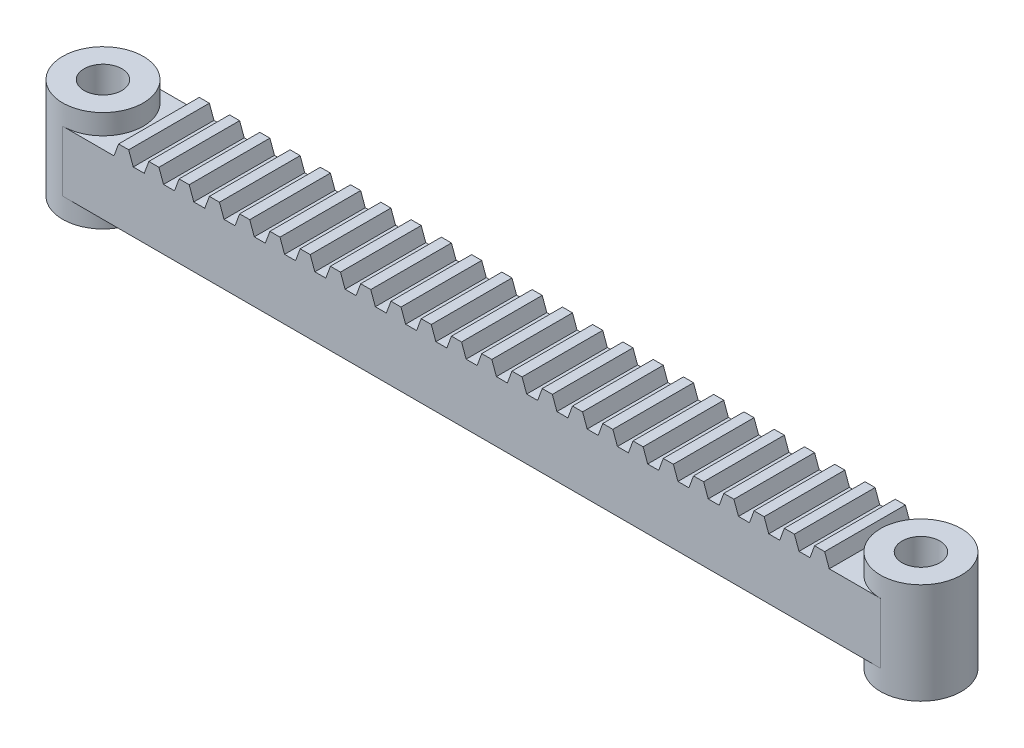
SolidWorks part; units mm, degrees
material "Galvanized Steel"
ref_plane "Front Plane" through (0, 0, 0) normal (0, 0, 1) x (1, 0, 0)
ref_plane "Top Plane" through (0, 0, 0) normal (0, 1, 0) x (1, 0, 0)
ref_plane "Right Plane" through (0, 0, 0) normal (1, 0, 0) x (0, 0, -1)
sketch "Sketch1" plane through (0, 0, 0) normal (0, 0, 1) x (1, 0, 0)
  line L0 (81.7719, 8.5) -> (83.7719, 8.5)
  line L1 (-75.138, 6) -> (-57.138, 6)
  line L3 (-75.138, -6) -> (102.6818, -6)
  line L17 (83.7719, 8.5) -> (81.7719, 8.5)
  line L19 (72.6818, 6) -> (74.862, 6)
  line L20 (81.7719, 8.5) -> (80.862, 6)
  line L21 (83.7719, 8.5) -> (84.6818, 6)
  line L22 (102.6818, 6) -> (102.6818, -6)
  line L23 (78.6818, 6) -> (80.862, 6)
  line L24 (77.7719, 8.5) -> (78.6818, 6)
  line L25 (75.7719, 8.5) -> (74.862, 6)
  line L26 (75.7719, 8.5) -> (77.7719, 8.5)
  line L27 (71.7719, 8.5) -> (72.6818, 6)
  line L28 (69.7719, 8.5) -> (68.862, 6)
  line L29 (69.7719, 8.5) -> (71.7719, 8.5)
  line L30 (65.7719, 8.5) -> (66.6818, 6)
  line L31 (63.7719, 8.5) -> (62.862, 6)
  line L32 (63.7719, 8.5) -> (65.7719, 8.5)
  line L33 (59.7719, 8.5) -> (60.6818, 6)
  line L34 (57.7719, 8.5) -> (56.862, 6)
  line L35 (57.7719, 8.5) -> (59.7719, 8.5)
  line L36 (53.7719, 8.5) -> (54.6818, 6)
  line L37 (51.7719, 8.5) -> (50.862, 6)
  line L38 (51.7719, 8.5) -> (53.7719, 8.5)
  line L39 (47.7719, 8.5) -> (48.6818, 6)
  line L40 (45.7719, 8.5) -> (44.862, 6)
  line L41 (45.7719, 8.5) -> (47.7719, 8.5)
  line L42 (41.7719, 8.5) -> (42.6818, 6)
  line L43 (39.7719, 8.5) -> (38.862, 6)
  line L44 (39.7719, 8.5) -> (41.7719, 8.5)
  line L45 (35.7719, 8.5) -> (36.6818, 6)
  line L46 (33.7719, 8.5) -> (32.862, 6)
  line L47 (33.7719, 8.5) -> (35.7719, 8.5)
  line L48 (29.7719, 8.5) -> (30.6818, 6)
  line L49 (27.7719, 8.5) -> (26.862, 6)
  line L50 (27.7719, 8.5) -> (29.7719, 8.5)
  line L51 (23.7719, 8.5) -> (24.6818, 6)
  line L52 (21.7719, 8.5) -> (20.862, 6)
  line L53 (21.7719, 8.5) -> (23.7719, 8.5)
  line L54 (17.7719, 8.5) -> (18.6818, 6)
  line L55 (15.7719, 8.5) -> (14.862, 6)
  line L56 (15.7719, 8.5) -> (17.7719, 8.5)
  line L57 (11.7719, 8.5) -> (12.6818, 6)
  line L58 (9.7719, 8.5) -> (8.862, 6)
  line L59 (9.7719, 8.5) -> (11.7719, 8.5)
  line L60 (5.7719, 8.5) -> (6.6818, 6)
  line L61 (3.7719, 8.5) -> (2.862, 6)
  line L62 (3.7719, 8.5) -> (5.7719, 8.5)
  line L63 (-0.2281, 8.5) -> (0.6818, 6)
  line L64 (-2.2281, 8.5) -> (-3.138, 6)
  line L65 (-2.2281, 8.5) -> (-0.2281, 8.5)
  line L66 (-6.2281, 8.5) -> (-5.3182, 6)
  line L67 (-8.2281, 8.5) -> (-9.138, 6)
  line L68 (-8.2281, 8.5) -> (-6.2281, 8.5)
  line L69 (-12.2281, 8.5) -> (-11.3182, 6)
  line L70 (-14.2281, 8.5) -> (-15.138, 6)
  line L71 (-14.2281, 8.5) -> (-12.2281, 8.5)
  line L72 (-18.2281, 8.5) -> (-17.3182, 6)
  line L73 (-20.2281, 8.5) -> (-21.138, 6)
  line L74 (-20.2281, 8.5) -> (-18.2281, 8.5)
  line L75 (-24.2281, 8.5) -> (-23.3182, 6)
  line L76 (-26.2281, 8.5) -> (-27.138, 6)
  line L77 (-26.2281, 8.5) -> (-24.2281, 8.5)
  line L78 (-30.2281, 8.5) -> (-29.3182, 6)
  line L79 (-32.2281, 8.5) -> (-33.138, 6)
  line L80 (-32.2281, 8.5) -> (-30.2281, 8.5)
  line L81 (-36.2281, 8.5) -> (-35.3182, 6)
  line L82 (-38.2281, 8.5) -> (-39.138, 6)
  line L83 (-38.2281, 8.5) -> (-36.2281, 8.5)
  line L84 (-42.2281, 8.5) -> (-41.3182, 6)
  line L85 (-44.2281, 8.5) -> (-45.138, 6)
  line L86 (-44.2281, 8.5) -> (-42.2281, 8.5)
  line L87 (-48.2281, 8.5) -> (-47.3182, 6)
  line L88 (-50.2281, 8.5) -> (-51.138, 6)
  line L89 (-50.2281, 8.5) -> (-48.2281, 8.5)
  line L90 (-54.2281, 8.5) -> (-53.3182, 6)
  line L91 (-56.2281, 8.5) -> (-57.138, 6)
  line L92 (-56.2281, 8.5) -> (-54.2281, 8.5)
  line L93 (-59.3182, 10.2872) -> (-59.3182, 6) construction
  line L94 (-75.138, 6) -> (-75.138, -6)
  line L95 (-53.3182, 6) -> (-51.138, 6)
  line L96 (-47.3182, 6) -> (-45.138, 6)
  line L97 (-41.3182, 6) -> (-39.138, 6)
  line L98 (-35.3182, 6) -> (-33.138, 6)
  line L99 (-29.3182, 6) -> (-27.138, 6)
  line L100 (-11.3182, 6) -> (-9.138, 6)
  line L101 (-17.3182, 6) -> (-15.138, 6)
  line L102 (-5.3182, 6) -> (-3.138, 6)
  line L103 (0.6818, 6) -> (2.862, 6)
  line L104 (-23.3182, 6) -> (-21.138, 6)
  line L105 (6.6818, 6) -> (8.862, 6)
  line L106 (12.6818, 6) -> (14.862, 6)
  line L107 (18.6818, 6) -> (20.862, 6)
  line L108 (84.6818, 6) -> (102.6818, 6)
  line L109 (66.6818, 6) -> (68.862, 6)
  line L110 (60.6818, 6) -> (62.862, 6)
  line L111 (54.6818, 6) -> (56.862, 6)
  line L112 (24.6818, 6) -> (26.862, 6)
  line L113 (30.6818, 6) -> (32.862, 6)
  line L114 (36.6818, 6) -> (38.862, 6)
  line L115 (42.6818, 6) -> (44.862, 6)
  line L116 (48.6818, 6) -> (50.862, 6)
  line L117 (86.862, 6) -> (86.862, 10.2872) construction
  point P0 (0, 0)
  dimension "D1" = 24
  dimension "D2" = 24
  dimension "D3" = 2
  dimension "D4" = 40
  dimension "D5" = 6
  dimension "D6" = 6
  dimension "D9" = 12
  dimension "D7" = 24
extrude "Boss-Extrude1" add sketch "Sketch1" along normal blind 16 contours L116 L39 L41 L40 L115 L42 L44 L43 L114 L45 L47 L46 L113 L48 L50 L49 L112 L51 L53 L52 L107 L54 L56 L55 L106 L57 L59 L58 L105 L60 L62 L61 L103 L63 L65 L64 L102 L66 L68 L67 L100 L69 L71 L70 L101 L72 L74 L73 L104 L75 L77 region at (13.7719, 0.5385, 0)
sketch "Sketch3" plane through (0, 6, 0) normal (0, 1, 0) x (1, 0, 0)
  line L1 (86.862, 0) -> (94.862, 0)
  line L2 (-59.3182, 0.9334) -> (-59.3182, -16) construction
  line L3 (-75.138, -16) -> (-57.138, -16) construction
  line L4 (86.862, 0) -> (86.862, -16)
  line L5 (84.6818, -16) -> (102.6818, -16) construction
  line L6 (-59.3182, -16) -> (-77.7063, -16)
  line L7 (-77.7063, -16) -> (-77.7063, 1.3823)
  line L8 (-77.7063, 1.3823) -> (-59.3182, 1.3823)
  line L9 (-59.3182, 1.3823) -> (-59.3182, -16)
  line L11 (86.862, -16) -> (94.862, -16)
  line L13 (94.862, 0) -> (104.4225, 2.0083)
  line L14 (104.4225, 2.0083) -> (106.3712, -17.332)
  line L15 (106.3712, -17.332) -> (91.3109, -17.9827)
  line L16 (91.3109, -17.9827) -> (94.862, -16)
  circle A0 centre (94.862, -8) radius 8
  circle A1 centre (-67.3182, -8) radius 8
  circle A2 centre (94.862, -8) radius 3.75
  circle A3 centre (-67.3182, -8) radius 3.75
  line M11 (102.6818, 0) -> (84.6818, 0)
  line M13 (84.6818, -16) -> (102.6818, -16)
  line M14 (102.6818, -16) -> (102.6818, 0)
  dimension "D1" = 16
  dimension "D2" = 16
  dimension "D3" = 7.5
  dimension "D4" = 7.5
extrude "Cut-Extrude1" cut sketch "Sketch3" against normal blind 16 contours A0 L16 L15 L14 L13 M14 M13 M11 | A0 M14 M11 | A0 M13 M14 | A2 region at (100.9066, 6, 1.6224) region at (99.6937, 6, -0.7592) region at (100.9066, 6, 14.3776)
sketch "Sketch4" plane through (0, 6, 0) normal (0, 1, 0) x (1, 0, 0)
  circle A0 centre (94.862, -8) radius 3.75 construction
  circle A1 centre (94.862, -8) radius 8 construction
  circle A2 centre (94.862, -8) radius 3.75
  circle A3 centre (94.862, -8) radius 8
extrude "Boss-Extrude2" add sketch "Sketch4" against normal blind 16
sketch "Sketch5" plane through (0, 6, 0) normal (0, 1, 0) x (1, 0, 0)
  line L3 (84.6818, -16) -> (94.862, -16)
  line L4 (94.862, 0) -> (84.6818, 0)
  line L5 (84.6818, 0) -> (84.6818, -16)
  circle A0 centre (94.862, -8) radius 3.75 construction
  arc A1 (94.862, -16) -> (94.862, 0) centre (94.862, -8) ccw
  arc A2 (94.862, -16) -> (94.862, 0) centre (94.862, -8) ccw
  circle A3 centre (94.862, -8) radius 8 construction
  circle A4 centre (94.862, -8) radius 3.75
  circle A5 centre (94.862, -8) radius 8
  arc M6 (94.862, -16) -> (94.862, 0) centre (94.862, -8) ccw
  dimension "D1" = 0
extrude "Boss-Extrude3" add sketch "Sketch5" along normal blind 4 contours A5 A4 M6 region at (87.0882, 6, 8)
sketch "Sketch6" plane through (0, 6, 0) normal (0, 1, 0) x (1, 0, 0)
  line L0 (-59.3182, 1.3823) -> (-59.3182, -16) construction
  line L1 (-59.3182, 1.3823) -> (-59.3182, -16)
  line L4 (-57.138, 0) -> (-75.138, 0)
  line L5 (-75.138, 0) -> (-75.138, -16)
  line L6 (-75.138, -16) -> (-57.138, -16)
  line L7 (-57.138, -16) -> (-57.138, 0)
  line L11 (-57.138, -16) -> (-57.138, 0)
  circle A0 centre (-67.3182, -8) radius 3.75 construction
  circle A1 centre (-67.3182, -8) radius 3.75
  circle A2 centre (-67.3182, -8) radius 8 construction
  circle A3 centre (-67.3182, -8) radius 8
  dimension "D1" = 0
extrude "Boss-Extrude4" add sketch "Sketch6" against normal blind 16 contours A1 | A3 region at (-67.3182, 6, 8)
sketch "Sketch7" plane through (0, 6, 0) normal (0, 1, 0) x (1, 0, 0)
  line L5 (-75.138, 0) -> (-75.138, -6.3118)
  line L6 (-75.138, -9.6882) -> (-75.138, -16)
  line L7 (-75.138, -16) -> (-57.138, -16)
  line L8 (-57.138, -16) -> (-57.138, 0)
  line L9 (-57.138, 0) -> (-75.138, 0)
  line L10 (-75.138, 0) -> (-75.138, -6.3118)
  line L11 (-75.138, -9.6882) -> (-75.138, -16)
  line L12 (-75.138, -16) -> (-67.3182, -16)
  line L13 (-57.138, -16) -> (-57.138, 0)
  line L14 (-67.3182, 0) -> (-75.138, 0)
  circle A0 centre (-67.3182, -8) radius 8 construction
  arc A1 (-75.138, -6.3118) -> (-75.138, -9.6882) centre (-67.3182, -8) ccw
  arc A2 (-75.138, -6.3118) -> (-75.138, -9.6882) centre (-67.3182, -8) ccw
  circle A3 centre (-67.3182, -8) radius 8
  circle A4 centre (-67.3182, -8) radius 3.75 construction
  circle A5 centre (-67.3182, -8) radius 3.75
  line M8 (-75.138, 0) -> (-75.138, -6.3118)
  line M10 (-75.138, -9.6882) -> (-75.138, -16)
  line M11 (-75.138, -16) -> (-57.138, -16)
  line M13 (-57.138, 0) -> (-75.138, 0)
  dimension "D1" = 0
extrude "Cut-Extrude2" cut sketch "Sketch7" against normal blind 16 contours A3 M13 M8 | A3 M10 M11 | A5 region at (-73.3628, 6, 1.6224) region at (-73.3628, 6, 14.3776)
sketch "Sketch8" plane through (0, 6, 0) normal (0, 1, 0) x (1, 0, 0)
  line L3 (-57.138, 0) -> (-67.3182, 0)
  line L4 (-67.3182, -16) -> (-57.138, -16)
  line L5 (-57.138, -16) -> (-57.138, 0)
  line L6 (-57.138, 0) -> (-67.3182, 0)
  line L7 (-67.3182, -16) -> (-57.138, -16)
  line L8 (-57.138, -16) -> (-57.138, 0)
  circle A0 centre (-67.3182, -8) radius 3.75 construction
  arc A1 (-67.3182, 0) -> (-67.3182, -16) centre (-67.3182, -8) ccw
  arc A2 (-67.3182, 0) -> (-67.3182, -16) centre (-67.3182, -8) ccw
  circle A3 centre (-67.3182, -8) radius 8 construction
  circle A4 centre (-67.3182, -8) radius 3.75
  circle A5 centre (-67.3182, -8) radius 8
  arc M6 (-67.3182, 0) -> (-67.3182, -16) centre (-67.3182, -8) ccw
  dimension "D1" = 0
extrude "Boss-Extrude5" add sketch "Sketch8" along normal blind 4 contours A5 A4 M6 region at (-61.8213, 6, 2.5031)
